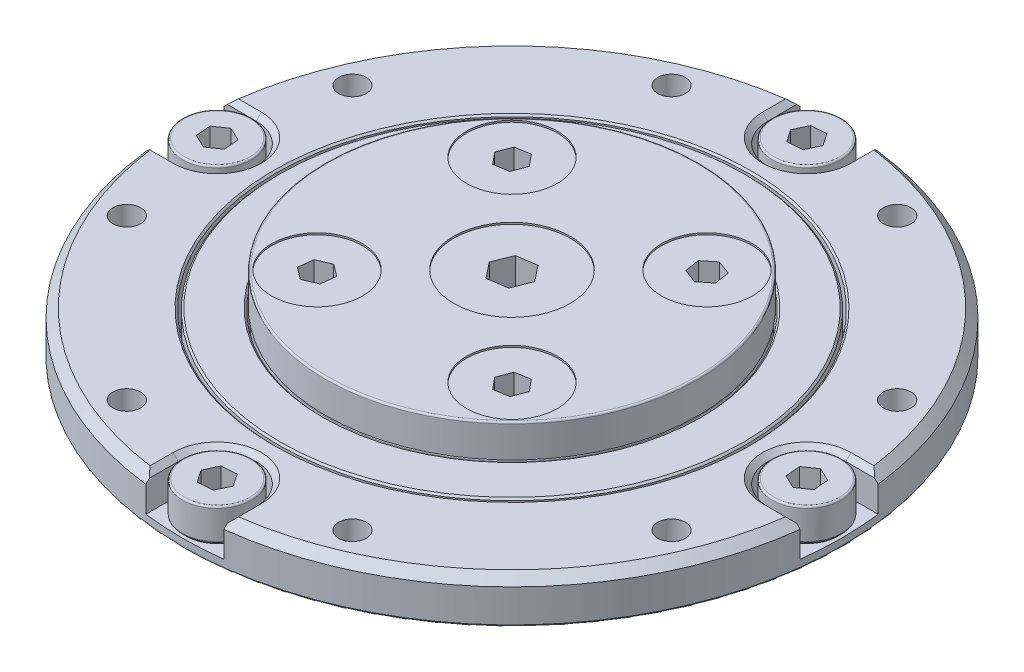
SolidWorks part; units mm, degrees
ref_plane "Front Plane" through (0, 0, 0) normal (0, 0, 1) x (1, 0, 0)
ref_plane "Top Plane" through (0, 0, 0) normal (0, 1, 0) x (1, 0, 0)
ref_plane "Right Plane" through (0, 0, 0) normal (1, 0, 0) x (0, 0, -1)
sketch "Sketch1" plane through (0, 0, 0) normal (0, 1, 0) x (1, 0, 0)
  circle A0 centre (0, 0) radius 19
  dimension "D1" = 38
extrude "Boss-Extrude1" add sketch "Sketch1" along normal blind 2.5
chamfer "Chamfer1" distance 0.5 angle 45 1 edges at (0, 2.5, 19)
sketch "Sketch2" plane through (0, 2.5, 0) normal (0, 1, 0) x (1, 0, 0)
  line L0 (0, 17) -> (0, 0) construction
  line L1 (-2.25, 17) -> (-2.25, 19.25)
  line L2 (-2.25, 19.25) -> (2.25, 19.25)
  line L3 (2.25, 19.25) -> (2.25, 17)
  circle A0 centre (0, 17) radius 2.25 construction
  arc A1 (-2.25, 17) -> (2.25, 17) centre (0, 17) ccw
  dimension "D1" = 4.5
  dimension "D2" = 17
extrude "Cut-Extrude1" cut sketch "Sketch2" against normal blind 2
chamfer "Chamfer2" distance 0.3 angle 45 3 edges at (2.25, 2.5, -17.6813) (0, 2.5, -14.75) (-2.25, 2.5, -17.6813)
sketch "Sketch3" plane through (0, 0.5, 0) normal (0, 1, 0) x (1, 0, 0)
  circle A0 centre (0, 17) radius 1.8
  dimension "D1" = 3.6
extrude "Boss-Extrude2" add sketch "Sketch3" along normal blind 0.4
sketch "Sketch4" plane through (0, 0.9, 0) normal (0, 1, 0) x (1, 0, 0)
  circle A0 centre (0, 17) radius 2
  dimension "D1" = 4
extrude "Boss-Extrude3" add sketch "Sketch4" along normal blind 1.6
chamfer "Chamfer3" distance 0.4 angle 45 1 edges at (0, 0.9, -15.2)
fillet "Fillet1" radius 0.1 2 edges at (0, 2.5, -15) (0, 0.7, -15)
sketch "Sketch5" plane through (0, 2.5, 0) normal (0, 1, 0) x (1, 0, 0)
  line L1 (-0.4907, 17.7136) -> (-0.8633, 16.9319)
  line L2 (-0.8633, 16.9319) -> (-0.3727, 16.2183)
  line L3 (-0.3727, 16.2183) -> (0.4907, 16.2864)
  line L4 (0.4907, 16.2864) -> (0.8633, 17.0681)
  line L5 (0.8633, 17.0681) -> (0.3727, 17.7817)
  line L6 (0.3727, 17.7817) -> (-0.4907, 17.7136)
  circle A0 centre (0, 17) radius 0.75 construction
  dimension "D1" = 1.5
extrude "Cut-Extrude2" cut sketch "Sketch5" against normal blind 1.5
pattern_circular "CirPattern1" count 4 every 90 about axis through (0, 0, 0) along (0, 1, 0) of "Cut-Extrude1", "Chamfer2", "Chamfer3", "Boss-Extrude2", "Boss-Extrude3", "Fillet1", "Cut-Extrude2"
sketch "Sketch6" plane through (0, 2.5, 0) normal (0, 1, 0) x (1, 0, 0)
  line L0 (0, 17) -> (0, 0) construction
  line L1 (-6.5056, 15.706) -> (0, 0) construction
  circle A2 centre (-6.5056, 15.706) radius 0.5
  dimension "D2" = 17
  dimension "D3" = 1
  dimension "D1" = 22.5
extrude "Cut-Extrude3" cut sketch "Sketch6" against normal through all both and the other way through all
hole_wizard "M2 Tapped Hole1" positions "Sketch7" profile "Sketch8" tap size "M2" standard "GB" end condition through all
sketch "Sketch7" plane through (0, 2.5, 0) normal (0, 1, 0) x (1, 0, 0)
  point P0 (-6.5056, 15.706)
sketch "Sketch8" plane through (-6.5056, 2.5, -15.706) normal (1, 0, 0) x (0, 0, 1)
  line L0 (0, 0) -> (0, 2.5)
  line L1 (0, 2.5) -> (0.8, 2.5)
  line L2 (0.8, 2.5) -> (0.8, 0)
  line L5 (0.8, 0) -> (0, 0)
  line L11 (0, -6.35) -> (0, 107.95) construction
  dimension "Thru Tap Drill Dia." = 1.6
  dimension "Thru Tap Drill Depth" = 2.5
pattern_circular "CirPattern2" count 8 every 45 about axis through (0, 0, 0) along (0, 1, 0) of "M2 Tapped Hole1"
sketch "Sketch9" plane through (0, 2.5, 0) normal (0, 1, 0) x (1, 0, 0)
  circle A0 centre (0, 0) radius 13.6397
  circle A1 centre (0, 0) radius 13.482
extrude "Cut-Extrude4" cut sketch "Sketch9" against normal blind 2.49
chamfer "Chamfer4" distance 0.1 angle 45 2 edges at (0, 2.5, 13.482) (0, 2.5, 13.6397)
sketch "Sketch11" plane through (0, 2.5, 0) normal (0, 1, 0) x (1, 0, 0)
  circle A0 centre (0, 0) radius 10.75 construction
  circle A1 centre (0, 0) radius 10.8233
  circle A2 centre (0, 0) radius 10.6676
  dimension "D1" = 21.5
extrude "Cut-Extrude5" cut sketch "Sketch11" against normal blind 2.49
chamfer "Chamfer5" distance 0.1 angle 45 2 edges at (0, 2.5, 10.6676) (0, 2.5, 10.8233)
sketch "Sketch12" plane through (0, 2.5, 0) normal (0, 1, 0) x (1, 0, 0)
  circle A0 centre (0, 0) radius 10.75
  dimension "D1" = 21.5
extrude "Boss-Extrude4" add sketch "Sketch12" along normal blind 1.9
fillet "Fillet2" radius 0.1 2 edges at (0, 2.4, 10.6676) (0, 4.4, 10.75)
sketch "Sketch13" plane through (0, 4.4, 0) normal (0, 1, 0) x (1, 0, 0)
  line L1 (5.621, -5.621) -> (-5.621, -5.621) construction
  line L2 (5.621, -5.621) -> (5.621, 5.621) construction
  line L3 (5.621, 5.621) -> (-5.621, 5.621) construction
  line L4 (-5.621, -5.621) -> (-5.621, 5.621) construction
  line L5 (5.621, -5.621) -> (-5.621, 5.621) construction
  line L6 (5.621, 5.621) -> (-5.621, -5.621) construction
  circle A2 centre (0, 0) radius 3.3576
  circle A4 centre (-5.621, 5.621) radius 2.6169
  circle A5 centre (5.621, 5.621) radius 2.6169
  circle A6 centre (5.621, -5.621) radius 2.6169
  circle A7 centre (-5.621, -5.621) radius 2.6169
  point P12 (5.4807, 5.4807)
  point P13 (5.621, 5.621)
extrude "Cut-Extrude6" cut sketch "Sketch13" against normal blind 0.1
sketch "Sketch14" plane through (0, 4.3, 0) normal (0, 1, 0) x (1, 0, 0)
  line L7 (4.9471, 5.0771) -> (5.7551, 4.7654)
  line L8 (5.7551, 4.7654) -> (6.429, 5.3093)
  line L9 (6.429, 5.3093) -> (6.2949, 6.1649)
  line L10 (6.2949, 6.1649) -> (5.4869, 6.4766)
  line L11 (5.4869, 6.4766) -> (4.813, 5.9327)
  line L12 (4.813, 5.9327) -> (4.9471, 5.0771)
  line L13 (-5.0713, 4.9518) -> (-4.7666, 5.7625)
  line L14 (-4.7666, 5.7625) -> (-5.3163, 6.4317)
  line L15 (-5.3163, 6.4317) -> (-6.1707, 6.2902)
  line L16 (-6.1707, 6.2902) -> (-6.4754, 5.4795)
  line L17 (-6.4754, 5.4795) -> (-5.9257, 4.8103)
  line L18 (-5.9257, 4.8103) -> (-5.0713, 4.9518)
  line L19 (-4.9271, -6.1392) -> (-4.8253, -5.2792)
  line L20 (-4.8253, -5.2792) -> (-5.5192, -4.761)
  line L21 (-5.5192, -4.761) -> (-6.3149, -5.1028)
  line L22 (-6.3149, -5.1028) -> (-6.4167, -5.9628)
  line L23 (-6.4167, -5.9628) -> (-5.7228, -6.481)
  line L24 (-5.7228, -6.481) -> (-4.9271, -6.1392)
  line L25 (6.1738, -6.2876) -> (6.4747, -5.4755)
  line L26 (6.4747, -5.4755) -> (5.9219, -4.8089)
  line L27 (5.9219, -4.8089) -> (5.0682, -4.9544)
  line L28 (5.0682, -4.9544) -> (4.7673, -5.7665)
  line L29 (4.7673, -5.7665) -> (5.3201, -6.4331)
  line L30 (5.3201, -6.4331) -> (6.1738, -6.2876)
  circle A1 centre (5.621, 5.621) radius 0.75 construction
  circle A2 centre (-5.621, 5.621) radius 0.75 construction
  circle A3 centre (-5.621, -5.621) radius 0.75 construction
  circle A4 centre (5.621, -5.621) radius 0.75 construction
  point P0 (-5.4985, 4.8811)
  dimension "D1" = 1.5
extrude "Cut-Extrude7" cut sketch "Sketch14" against normal blind 1.5
sketch "Sketch15" plane through (0, 4.3, 0) normal (0, 1, 0) x (1, 0, 0)
  line L1 (-0.4265, -1.0731) -> (0.7161, -0.9059)
  line L2 (0.7161, -0.9059) -> (1.1425, 0.1672)
  line L3 (1.1425, 0.1672) -> (0.4265, 1.0731)
  line L4 (0.4265, 1.0731) -> (-0.7161, 0.9059)
  line L5 (-0.7161, 0.9059) -> (-1.1425, -0.1672)
  line L6 (-1.1425, -0.1672) -> (-0.4265, -1.0731)
  circle A0 centre (0, 0) radius 1 construction
  dimension "D1" = 2
extrude "Cut-Extrude8" cut sketch "Sketch15" against normal blind 2
fillet "Fillet3" radius 0.1 1 edges at (0, 0, 19)
